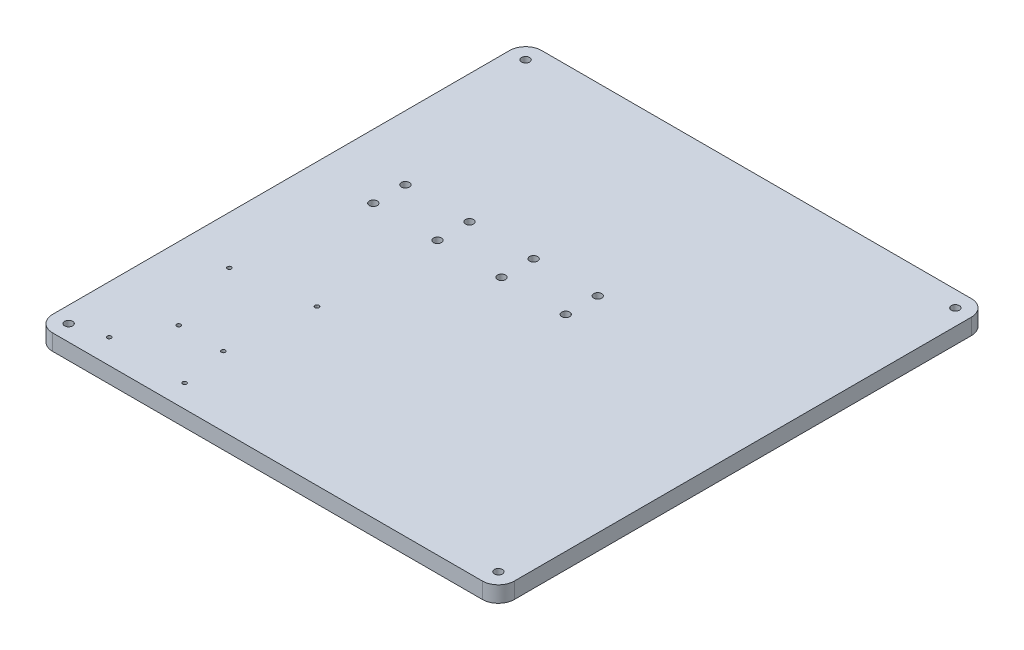
SolidWorks part; units mm, degrees
ref_plane "Front Plane" through (0, 0, 0) normal (0, 0, 1) x (1, 0, 0)
ref_plane "Top Plane" through (0, 0, 0) normal (0, 1, 0) x (1, 0, 0)
ref_plane "Right Plane" through (0, 0, 0) normal (1, 0, 0) x (0, 0, -1)
sketch "Sketch1" plane through (0, 0, 0) normal (0, 1, 0) x (1, 0, 0)
  line L0 (45.3825, 61.2661) -> (45.3825, -243.7339) construction
  line L1 (-98.6175, 61.2661) -> (189.3825, 61.2661)
  line L2 (-98.6175, 61.2661) -> (-98.6175, -243.7339)
  line L3 (-98.6175, -243.7339) -> (189.3825, -243.7339)
  line L4 (189.3825, 61.2661) -> (189.3825, -243.7339)
  line L5 (-98.6175, -91.2339) -> (189.3825, -91.2339) construction
  circle A0 centre (-58.6175, -53.7339) radius 2.5
  circle A1 centre (-18.6175, -53.7339) radius 2.5
  circle A2 centre (21.3825, -53.7339) radius 2.5
  circle A3 centre (61.3825, -53.7339) radius 2.5
  circle A4 centre (-18.6175, -73.7339) radius 2.5
  circle A5 centre (21.3825, -73.7339) radius 2.5
  circle A6 centre (61.3825, -73.7339) radius 2.5
  circle A7 centre (-58.6175, -73.7339) radius 2.5
  circle A8 centre (-88.6175, 51.2661) radius 2.5
  circle A9 centre (179.3825, 51.2661) radius 2.5
  circle A10 centre (179.3825, -233.7339) radius 2.5
  circle A11 centre (-88.6175, -233.7339) radius 2.5
  circle A12 centre (-68.6175, -228.4339) radius 1.25
  circle A13 centre (-20.4175, -229.5839) radius 1.25
  circle A14 centre (-53.4175, -200.3473) radius 1.25
  circle A15 centre (-25.5175, -200.3473) radius 1.25
  circle A16 centre (-68.6175, -153.5339) radius 1.25
  circle A17 centre (-20.4175, -147.0339) radius 1.25
  point P42 (0, 0)
  dimension "D4" = 40
  dimension "D5" = 5
  dimension "D8" = 5
  dimension "D9" = 10
  dimension "D10" = 10
  dimension "D11" = 2.5
  dimension "D12" = 15.3
  dimension "D13" = 30
  dimension "D14" = 2.5
  dimension "D15" = 1.15
  dimension "D16" = 2.5
  dimension "D17" = 74.9
  dimension "D18" = 2.5
  dimension "D19" = 2.5
  dimension "D23" = 2.5
  dimension "D1" = 288
  dimension "D2" = 305
  dimension "D3" = 115
  dimension "D20" = 27.9
  dimension "D21" = 15.2
  dimension "D22" = 5.1
  dimension "D24" = 82.55
  dimension "D25" = 73.7339
  dimension "D26" = 200.3473
  dimension "D6" = 4
  dimension "D7" = 2
extrude "Boss-Extrude1" add sketch "Sketch1" along normal blind 10
fillet "Fillet1" radius 10 4 edges at (189.3825, 5, -61.2661) (189.3825, 5, 243.7339) (-98.6175, 5, 243.7339) (-98.6175, 5, -61.2661)
